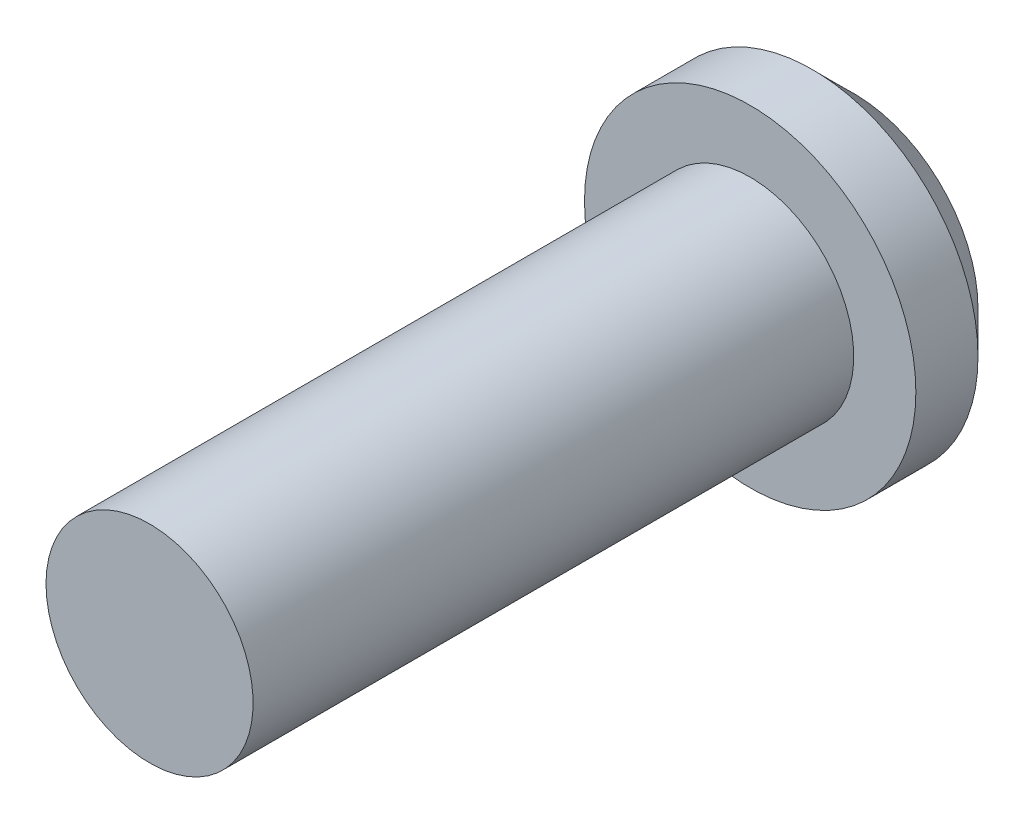
SolidWorks part; units mm, degrees
ref_plane "Front Plane" through (0, 0, 0) normal (0, 0, 1) x (1, 0, 0)
ref_plane "Top Plane" through (0, 0, 0) normal (0, 1, 0) x (1, 0, 0)
ref_plane "Right Plane" through (0, 0, 0) normal (1, 0, 0) x (0, 0, -1)
sketch "Sketch2" plane through (0, 0, 0) normal (0, 0, 1) x (1, 0, 0)
  circle A0 centre (0, 0) radius 2.5
  circle A1 centre (0, 0) radius 4
  dimension "D1" = 5
  dimension "D2" = 8
extrude "Boss-Extrude1" add sketch "Sketch2" along normal blind 2.5 contours A1
extrude "Boss-Extrude2" add sketch "Sketch2<6>" along normal up to surface (2.5 mm away) up to face at (4, 0, 2.5)
sketch "Sketch2<6>" plane through (0, 0, 0) normal (0, 0, 1) x (1, 0, 0) same geometry as "Sketch2"
sketch "Sketch3" plane through (0, 0, 2.5) normal (0, 0, 1) x (1, 0, 0)
  circle A0 centre (0, 0) radius 2.5
  dimension "D1" = 5
extrude "Boss-Extrude3" add sketch "Sketch3" along normal blind 14.5 contours A0
chamfer "Chamfer2" distance 1 angle 45 1 edges at (4, 0, 0)
sketch "Sketch4" plane through (0, 0, 0) normal (0, 0, -1) x (-1, 0, 0)
  line L1 (-0.8704, 2.8344) -> (-2.8899, 0.6634)
  line L2 (-2.8899, 0.6634) -> (-2.0195, -2.171)
  line L3 (-2.0195, -2.171) -> (0.8704, -2.8344)
  line L4 (0.8704, -2.8344) -> (2.8899, -0.6634)
  line L5 (2.8899, -0.6634) -> (2.0195, 2.171)
  line L6 (2.0195, 2.171) -> (-0.8704, 2.8344)
  circle A0 centre (0, 0) radius 2.5678 construction
extrude "Cut-Extrude1" cut sketch "Sketch4" against normal blind 1.5
